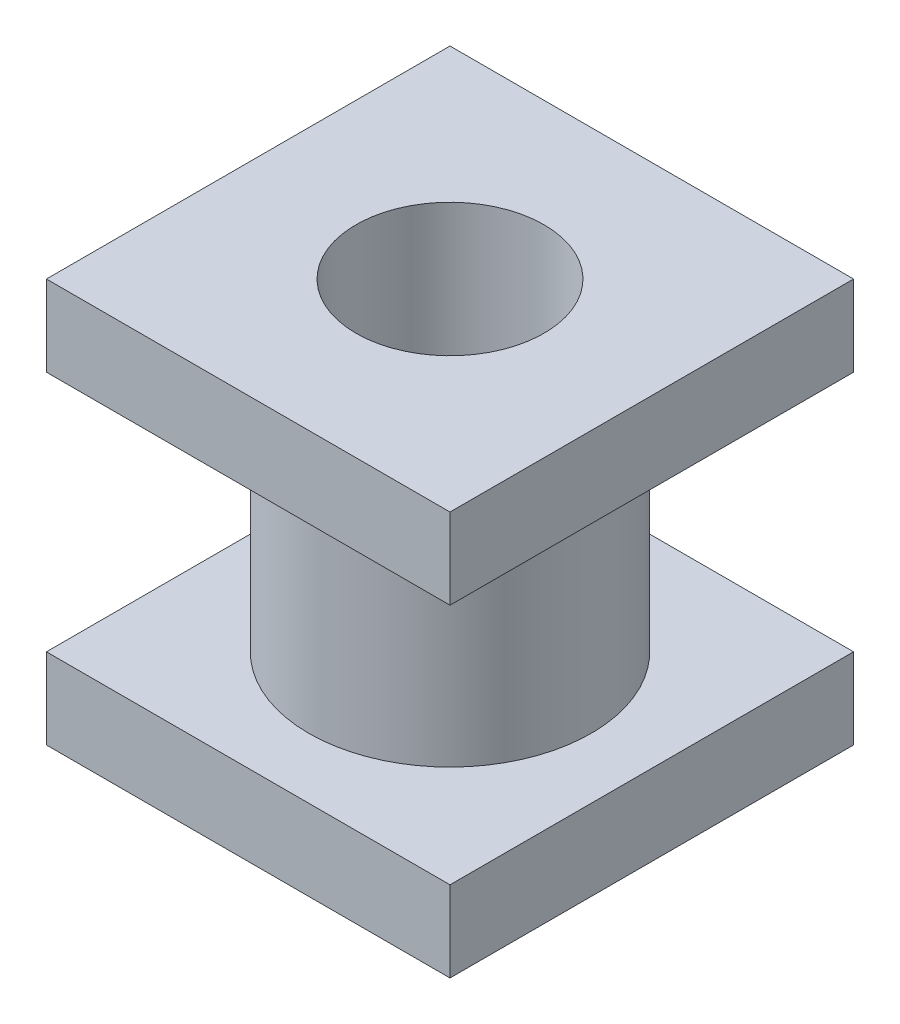
SolidWorks part; units mm, degrees
ref_plane "Front Plane" through (0, 0, 0) normal (0, 0, 1) x (1, 0, 0)
ref_plane "Top Plane" through (0, 0, 0) normal (0, 1, 0) x (1, 0, 0)
ref_plane "Right Plane" through (0, 0, 0) normal (1, 0, 0) x (0, 0, -1)
sketch "Sketch1" plane through (0, 0, 0) normal (0, 1, 0) x (1, 0, 0)
  line L1 (0, 0) -> (10, 0)
  line L2 (0, 0) -> (0, -10)
  line L3 (0, -10) -> (10, -10)
  line L4 (10, 0) -> (10, -10)
  circle A0 centre (5, -5) radius 3.5
  point P6 (5, 0)
  point P8 (10, -5)
  dimension "D2" = 7
  dimension "D1" = 10
extrude "Boss-Extrude1" add sketch "Sketch1" along normal blind 2
extrude "Boss-Extrude2" add sketch "Sketch1<2>" along normal blind 10 contours A0 region at (5, 0, 5)
sketch "Sketch1<2>" plane through (0, 0, 0) normal (0, 1, 0) x (1, 0, 0) same geometry as "Sketch1"
extrude "Boss-Extrude4" add sketch "Sketch1<4>" against normal blind 2 from surface starting at face at (5, 10, 8.5)
sketch "Sketch1<4>" plane through (0, 0, 0) normal (0, 1, 0) x (1, 0, 0) same geometry as "Sketch1"
sketch "Sketch2" plane through (0, 10, 0) normal (0, 1, 0) x (1, 0, 0)
  line L0 (10, -10) -> (0, -10) construction
  line L1 (0, -10) -> (0, 0) construction
  circle A0 centre (5, -5) radius 2.3304
  point P2 (0, 0)
  point P5 (5, -10)
  point P8 (0, -5)
extrude "Cut-Extrude1" cut sketch "Sketch2" against normal through all
